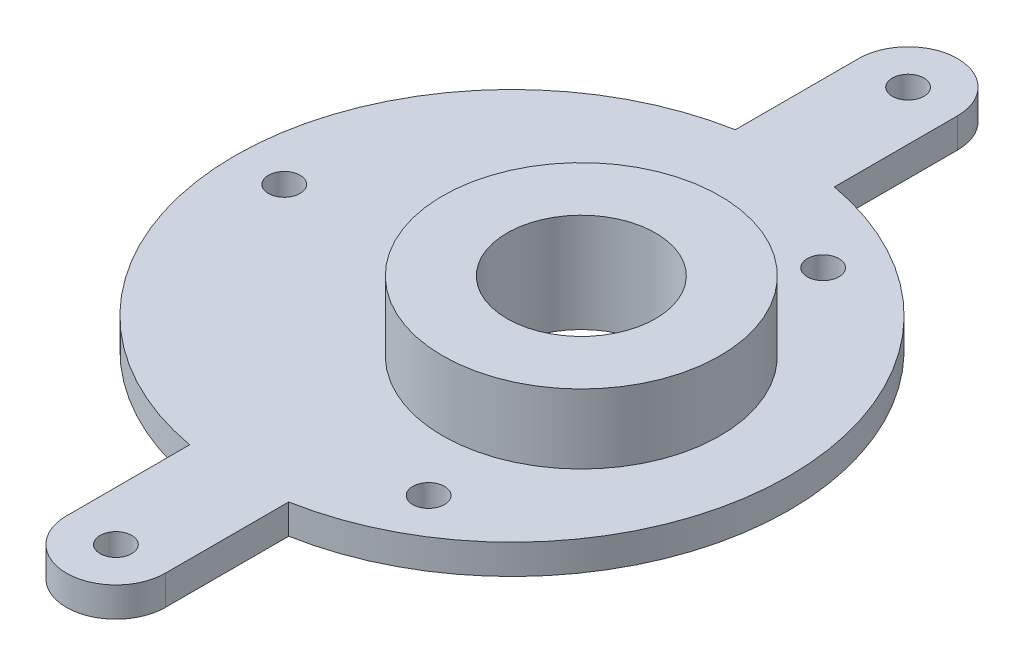
SolidWorks part; units mm, degrees
ref_plane "正面" through (0, 0, 0) normal (0, 0, 1) x (1, 0, 0)
ref_plane "平面" through (0, 0, 0) normal (0, 1, 0) x (1, 0, 0)
ref_plane "右側面" through (0, 0, 0) normal (1, 0, 0) x (0, 0, -1)
sketch "ｽｹｯﾁ1" plane through (0, 0, 0) normal (0, 1, 0) x (1, 0, 0)
  line L0 (0, 40) -> (0, -40) construction
  line L1 (5, 40) -> (5, 27.55)
  line L2 (-5, 40) -> (-5, 27.55)
  line L3 (-5, -27.55) -> (-5, -40)
  line L4 (5, -27.55) -> (5, -40)
  arc A3 (-5, 27.55) -> (-5, -27.55) centre (0, 0) ccw
  arc A4 (5, 40) -> (-5, 40) centre (0, 40) ccw
  arc A5 (-5, -40) -> (5, -40) centre (0, -40) ccw
  arc A6 (5, -27.55) -> (5, 27.55) centre (0, 0) ccw
  circle A7 centre (0, 40) radius 1.6
  circle A8 centre (0, -40) radius 1.6
  point P9 (0, 0)
  point P20 (0, 0)
  dimension "D3" = 3.2
  dimension "D8" = 28
  dimension "D6" = 80
  dimension "D7" = 10
extrude "ﾎﾞｽ - 押し出し1" add sketch "ｽｹｯﾁ1" along normal blind 3
sketch "ｽｹｯﾁ4" plane through (0, 3, 0) normal (0, 1, 0) x (1, 0, 0)
  circle A0 centre (7, 0) radius 14
  point P2 (0, 0)
  point P4 (0, 0)
  dimension "D1" = 28
  dimension "D2" = 7
extrude "ﾎﾞｽ - 押し出し2" add sketch "ｽｹｯﾁ4" along normal blind 7
sketch "ｽｹｯﾁ2" plane through (0, 3, 0) normal (0, 1, 0) x (1, 0, 0)
  circle A0 centre (7, 0) radius 7.5
  point P3 (0, 0)
  point P5 (7, 0)
  point P6 (0, 0)
  point P7 (7, 0)
  point P8 (-7, 0)
  point P9 (7, 0)
  point P10 (0, 0)
  dimension "D1" = 15
  dimension "D2" = 7
extrude "ｶｯﾄ - 押し出し1" cut sketch "ｽｹｯﾁ2" against normal through all both and the other way through all
sketch "ｽｹｯﾁ3" plane through (0, 3, 0) normal (0, 1, 0) x (1, 0, 0)
  circle A0 centre (-23, 0) radius 1.6
  circle A1 centre (0, 0) radius 23 construction
  circle A2 centre (11.5, 19.9186) radius 1.6
  circle A3 centre (11.5, -19.9186) radius 1.6
  point P7 (0, 0)
  point P8 (0, 0)
  point P11 (0, 0)
  point P12 (-23, 0)
  point P13 (23, 0)
  point P14 (-23, 0)
  dimension "D1" = 46
  dimension "D2" = 3.2
  dimension "D3" = 3
extrude "ｶｯﾄ - 押し出し2" cut sketch "ｽｹｯﾁ3" against normal through all
